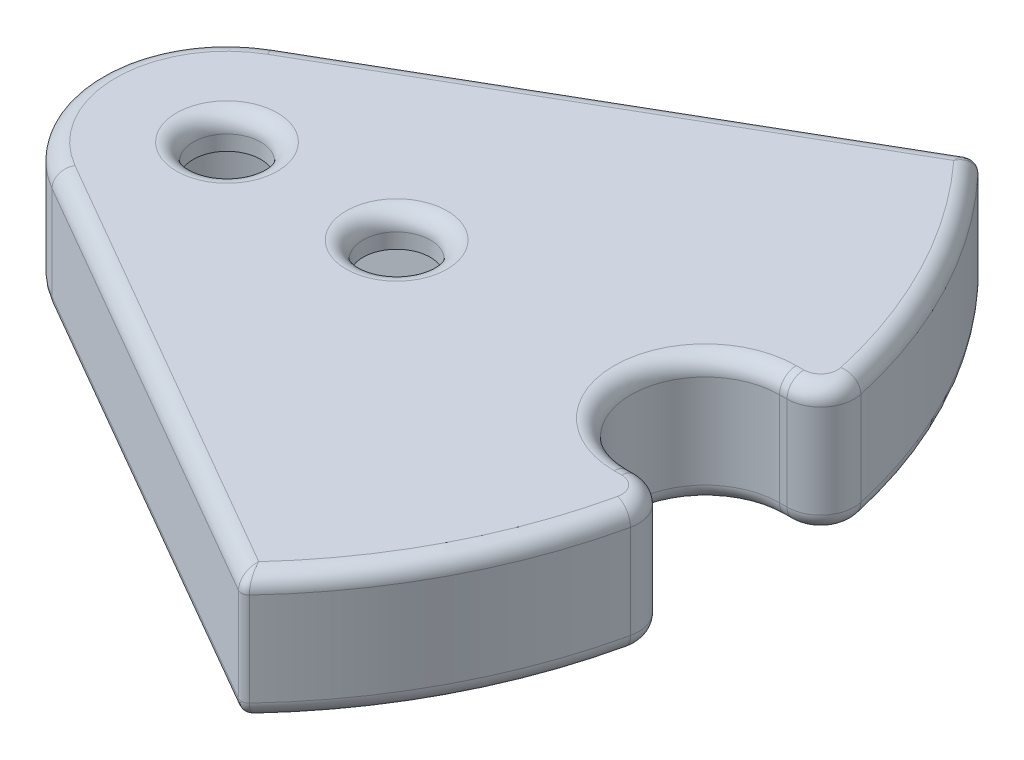
SolidWorks part; units mm, degrees
ref_plane "Front Plane" through (0, 0, 0) normal (0, 0, 1) x (1, 0, 0)
ref_plane "Top Plane" through (0, 0, 0) normal (0, 1, 0) x (1, 0, 0)
ref_plane "Right Plane" through (0, 0, 0) normal (1, 0, 0) x (0, 0, -1)
sketch "Sketch1" plane through (0, 0, 0) normal (0, 1, 0) x (1, 0, 0)
  line L0 (2.2864, 2.65) -> (14.1103, 1.997)
  line L1 (2.2864, -2.65) -> (14.1103, -1.997)
  line L2 (0, 0) -> (14, 0) construction
  line L3 (16, 0) -> (19.05, 0) construction
  line L4 (-3.02, 5.2308) -> (17.7867, 17.2435)
  line L5 (19.05, 0) -> (25.05, 0) construction
  line L6 (22.55, 3.5) -> (24.8043, 3.5)
  line L7 (22.55, -3.5) -> (24.8043, -3.5)
  line L8 (-3.02, -5.2308) -> (17.7867, -17.2435)
  circle A0 centre (0, 0) radius 3.5 construction
  arc A1 (14.1103, 1.997) -> (14.1103, -1.997) centre (14, 0) cw
  arc A2 (2.2864, 2.65) -> (2.2864, -2.65) centre (0, 0) ccw
  circle A3 centre (14, 0) radius 0.5 construction
  circle A4 centre (12, 0) radius 0.5 construction
  circle A5 centre (10, 0) radius 0.5 construction
  circle A6 centre (8, 0) radius 0.5 construction
  circle A7 centre (6, 0) radius 0.5 construction
  circle A8 centre (4, 0) radius 0.5 construction
  arc A9 (18.2323, 17.1781) -> (24.8043, 3.5) centre (0, 0) cw
  arc A11 (22.55, 3.5) -> (22.55, -3.5) centre (22.55, 0) ccw
  arc A12 (-3.02, -5.2308) -> (-3.02, 5.2308) centre (0, 0) cw
  arc A13 (18.2323, 17.1781) -> (17.7867, 17.2435) centre (17.9681, 16.9292) ccw
  arc A15 (18.2323, -17.1781) -> (24.8043, -3.5) centre (0, 0) ccw
  arc A16 (18.2323, -17.1781) -> (17.7867, -17.2435) centre (17.9681, -16.9292) cw
  point P4 (16, 0)
  point P6 (-3.5, 0)
  dimension "D1" = 7
  dimension "D5" = 1
  dimension "D8" = 2.54
  dimension "D10" = 3.5
  dimension "D4" = 2
  dimension "D2" = 19.5
  dimension "D3" = 5.3
  dimension "D7" = 2
  dimension "D9" = 6
  dimension "D11" = 30
  dimension "D12" = 19.05
  dimension "D6" = 6
extrude "Boss-Extrude1" add sketch "Sketch1" along normal blind 4.5
sketch "Sketch2" plane through (0, 4.5, 0) normal (0, 1, 0) x (1, 0, 0)
  line L0 (0, 0) -> (16, 0) construction
  line L4 (17.7867, 17.2435) -> (-3.02, 5.2308)
  line L5 (-3.02, -5.2308) -> (17.7867, -17.2435)
  line L6 (24.8043, -3.5) -> (22.55, -3.5)
  line L7 (22.55, 3.5) -> (24.8043, 3.5)
  line L8 (17.7867, 17.2435) -> (-3.02, 5.2308)
  line L9 (-3.02, -5.2308) -> (17.7867, -17.2435)
  line L10 (24.8043, -3.5) -> (22.55, -3.5)
  line L11 (22.55, 3.5) -> (24.8043, 3.5)
  circle A0 centre (0, 0) radius 1.5875
  circle A1 centre (8, 0) radius 1.5875
  arc A2 (14.1103, -1.997) -> (14.1103, 1.997) centre (14, 0) ccw construction
  arc A8 (18.2323, 17.1781) -> (17.7867, 17.2435) centre (17.9681, 16.9292) ccw
  arc A9 (-3.02, 5.2308) -> (-3.02, -5.2308) centre (0, 0) ccw
  arc A10 (17.7867, -17.2435) -> (18.2323, -17.1781) centre (17.9681, -16.9292) ccw
  arc A11 (18.2323, -17.1781) -> (24.8043, -3.5) centre (0, 0) ccw
  arc A13 (22.55, 3.5) -> (22.55, -3.5) centre (22.55, 0) ccw
  arc A15 (24.8043, 3.5) -> (18.2323, 17.1781) centre (0, 0) ccw
  arc A16 (18.2323, 17.1781) -> (17.7867, 17.2435) centre (17.9681, 16.9292) ccw
  arc A17 (-3.02, 5.2308) -> (-3.02, -5.2308) centre (0, 0) ccw
  arc A18 (17.7867, -17.2435) -> (18.2323, -17.1781) centre (17.9681, -16.9292) ccw
  arc A19 (18.2323, -17.1781) -> (24.8043, -3.5) centre (0, 0) ccw
  arc A21 (22.55, 3.5) -> (22.55, -3.5) centre (22.55, 0) ccw
  arc A23 (24.8043, 3.5) -> (18.2323, 17.1781) centre (0, 0) ccw
  point P15 (8, 0)
  dimension "D2" = 3.175
  dimension "D3" = 3.175
  dimension "D1" = 0
extrude "Boss-Extrude2" add sketch "Sketch2" along normal offset from surface (1.5 mm away) 6 up to face at (15.6331, 0, 0)
fillet "Fillet1" radius 1.5875 2 edges at (24.8043, 3, 3.5) (24.8043, 3, -3.5)
fillet "Fillet2" radius 0.7937 16 edges at (8.1983, 0, -2.3235) (16, 0, 0) (8.1983, 0, 2.3235) (-3.5, 0, 0) (19.05, 0, 0) (22.7271, 0, -3.5) (24.1426, 0, -4.0941) (22.1365, 0, -11.7251) (18.0208, 0, -17.2883) (7.3833, 0, -11.2372) (-6.04, 0, 0) (7.3833, 0, 11.2372) (18.0208, 0, 17.2883) (22.1365, 0, 11.7251) (24.1426, 0, 4.0941) (22.7271, 0, 3.5)
fillet "Fillet3" radius 0.7937 14 edges at (18.0208, 6, 17.2883) (7.3833, 6, 11.2372) (-6.04, 6, 0) (7.3833, 6, -11.2372) (18.0208, 6, -17.2883) (22.1365, 6, -11.7251) (24.1426, 6, -4.0941) (22.7271, 6, -3.5) (19.05, 6, 0) (22.7271, 6, 3.5) (24.1426, 6, 4.0941) (22.1365, 6, 11.7251) (0, 6, 1.5875) (8, 6, 1.5875)
